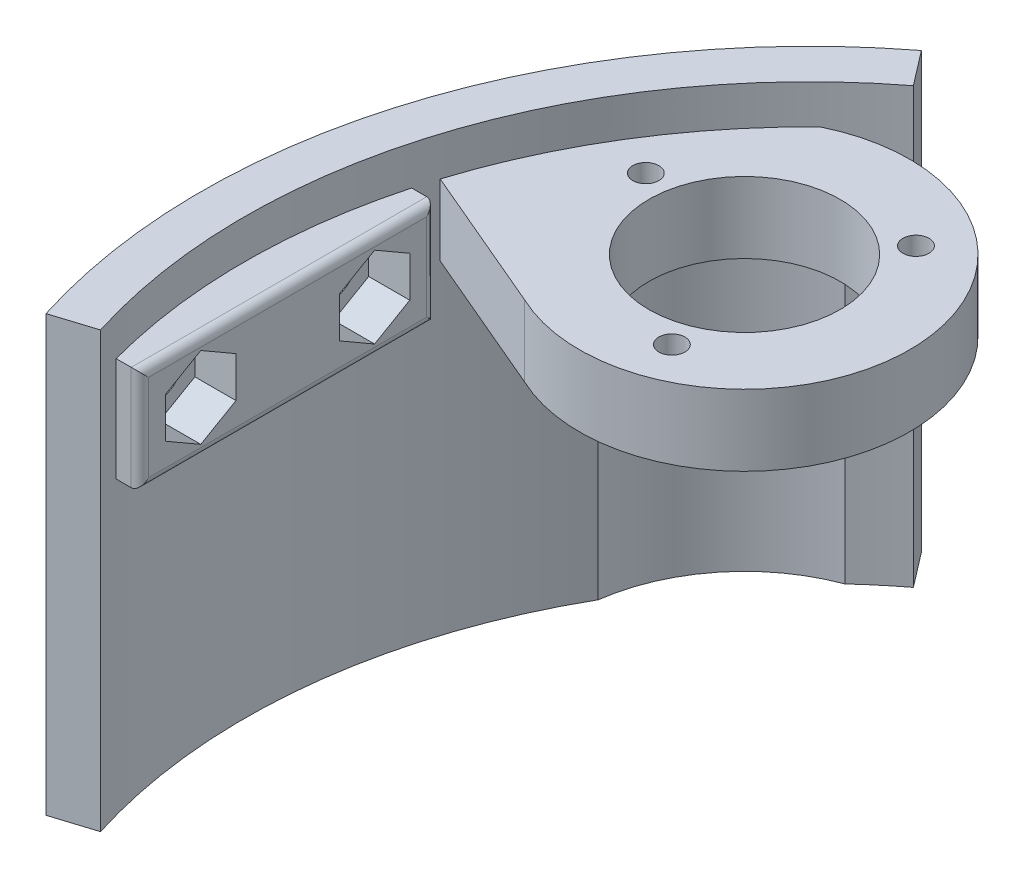
SolidWorks part; units mm, degrees
ref_plane "Front Plane" through (0, 0, 0) normal (0, 0, 1) x (1, 0, 0)
ref_plane "Top Plane" through (0, 0, 0) normal (0, 1, 0) x (1, 0, 0)
ref_plane "Right Plane" through (0, 0, 0) normal (1, 0, 0) x (0, 0, -1)
sketch "Sketch1" plane through (0, 0, 0) normal (0, 1, 0) x (1, 0, 0)
  line L2 (-66.7602, 21.0494) -> (0, 0)
  line L3 (0, 0) -> (-66.7602, -21.0494)
  line L4 (0, 0) -> (-66.7602, 21.0494)
  line L5 (-42.6133, 55.5347) -> (0, 0)
  line L6 (0, 0) -> (-61.9916, 19.5459) construction
  line L7 (0, 0) -> (-39.5695, 51.568) construction
  arc A0 (-66.7602, 21.0494) -> (-66.7602, -21.0494) centre (0, 0) ccw
  arc A1 (-61.9916, 19.5459) -> (-61.9916, -19.5459) centre (0, 0) ccw
  arc A2 (-39.5695, 51.568) -> (-61.9916, 19.5459) centre (0, 0) ccw
  arc A3 (-42.6133, 55.5347) -> (-66.7602, 21.0494) centre (0, 0) ccw
  point P8 (-65, 0)
  dimension "D1" = 140
  dimension "D2" = 5
  dimension "D3" = 35
  dimension "D5" = 35
  dimension "D4" = 2
extrude "Boss-Extrude1" add sketch "Sketch1" along normal blind 50 contours A1 L2 A0 L3 | L5 A3 L2 A2 region at (-54.462, 0, -38.1347) region at (-66.4858, 0, 0)
sketch "Sketch2" plane through (0, 0, 0) normal (0, 1, 0) x (1, 0, 0)
  line L0 (-66.7602, -21.0494) -> (-38.1487, -12.0282)
  line L1 (-38.1487, -12.0282) -> (0, -15.5)
  line L2 (0, -15.5) -> (0, 15.5)
  line L3 (0, 15.5) -> (-39.2471, 7.7244)
  line L4 (-67.8367, 13.3512) -> (-39.2471, 7.7244)
  circle A0 centre (0, 0) radius 40
  circle A1 centre (0, 0) radius 69.138
  arc A2 (-2.798, -15.2454) -> (-5.9097, 14.3292) centre (0, 0) ccw
  dimension "D1" = 80
  dimension "D2" = 31
extrude "Boss-Extrude2" add sketch "Sketch2" along normal blind 5 contours L4 A1 L0 A0 region at (-55.2007, 0, 3.0696)
sketch "Sketch3" plane through (0, 0, 0) normal (0, -1, 0) x (1, 0, 0)
  line L0 (-47.6858, 15.0353) -> (-38.1487, 12.0282)
  line L1 (-39.2471, -7.7244) -> (-49.0589, -9.6555)
  arc A0 (-38.1487, 12.0282) -> (-39.2471, -7.7244) centre (0, 0) ccw construction
  arc A1 (-38.1487, 12.0282) -> (-39.2471, -7.7244) centre (0, 0) ccw
  arc A2 (-47.6858, 15.0353) -> (-49.0589, -9.6555) centre (0, 0) ccw
  dimension "D1" = 10
extrude "Boss-Extrude3" add sketch "Sketch3" along normal blind 8.5
sketch "Sketch4" plane through (0, 0, 0) normal (0, 1, 0) x (1, 0, 0)
  line L0 (-66.7602, -21.0494) -> (-38.1487, -12.0282) construction
  line L1 (-38.1487, -12.0282) -> (0, -15.5) construction
  line L2 (0, -15.5) -> (0, 15.5) construction
  line L3 (0, 15.5) -> (-39.2471, 7.7244) construction
  line L4 (-67.8367, 13.3512) -> (-39.2471, 7.7244) construction
  line L5 (-66.7602, -21.0494) -> (-38.1487, -12.0282)
  line L6 (-38.1487, -12.0282) -> (0, -15.5)
  line L7 (0, -15.5) -> (0, 15.5)
  line L8 (0, 15.5) -> (-39.2471, 7.7244)
  line L9 (-67.8367, 13.3512) -> (-39.2471, 7.7244)
  circle A0 centre (0, 0) radius 15.5
  circle A1 centre (0, 0) radius 69.138
  circle A2 centre (0, 0) radius 69.138
  circle A3 centre (0, 0) radius 40
  circle A4 centre (0, 0) radius 40
  dimension "D1" = 0
  dimension "D2" = 0
extrude "Boss-Extrude4" add sketch "Sketch4" along normal blind 5 from surface contours L8 A4 L6 L7 | A0 region at (-25.3301, 0, 1.4883) starting at face at (-44.2329, -8.5, 2.4597)
sketch "Sketch5" plane through (0, -3.5, 0) normal (0, 1, 0) x (1, 0, 0)
  circle A0 centre (0, 0) radius 15.5
extrude "Boss-Extrude5" add sketch "Sketch5" along normal blind 7.17
sketch "Sketch7" plane through (0, 50, 0) normal (0, 1, 0) x (1, 0, 0)
  line L0 (-36.961, 29.5317) -> (-36.961, 0) construction
  line L1 (-36.961, 0) -> (0, 0) construction
  line L2 (0, 0) -> (-36.961, 29.5317) construction
  line L3 (-61.9916, 19.5459) -> (-45.0708, 12.3494)
  line L4 (-39.5695, 51.568) -> (-37.2381, 48.5297)
  line L6 (-42.6133, 55.5347) -> (-39.5695, 51.568) construction
  circle A0 centre (-36.961, 29.5317) radius 19
  arc A3 (-39.5695, 51.568) -> (-61.9916, -19.5459) centre (0, 0) ccw construction
  arc A4 (-39.5695, 51.568) -> (-61.9916, -19.5459) centre (0, 0) ccw
  arc M5 (-61.9916, -19.5459) -> (-39.5695, 51.568) centre (0, 0) cw
  dimension "D1" = 38
  dimension "D2" = 47.31
extrude "Boss-Extrude6" add sketch "Sketch7" against normal blind 8.18 from offset 4.5 contours A0 L4 L3 M5 | A0 region at (-56.4968, 50, -21.8557) region at (-36.7795, 50, -29.3867) offset against normal yes
sketch "Sketch8" plane through (0, 50, 0) normal (0, 1, 0) x (1, 0, 0)
  circle A0 centre (-36.961, 29.5317) radius 11
  circle A1 centre (-27.9647, 40.2587) radius 1.5
  circle A2 centre (-32.1693, 16.3773) radius 1.5
  circle A3 centre (-50.7489, 31.9592) radius 1.5
  point P12 (-36.961, 29.5317)
  dimension "D1" = 22
  dimension "D2" = 3
  dimension "D3" = 14
  dimension "D4" = 3
extrude "Cut-Extrude2" cut sketch "Sketch8" against normal up to next
sketch "Sketch10" plane through (0, 0, 0) normal (1, 0, 0) x (0, 0, -1)
  circle A0 centre (-10, 39.5) radius 2.55
  circle A1 centre (10, 39.5) radius 2.55
  dimension "D1" = 5.1
  dimension "D2" = 20
  dimension "D3" = 10
  dimension "D4" = 44.33
extrude "Cut-Extrude5" cut sketch "Sketch10" along normal up to next from offset 90 offset against normal yes
sketch "Sketch11" plane through (0, 0, 0) normal (1, 0, 0) x (0, 0, -1)
  line L1 (-10, 34.8235) -> (-5.95, 37.1617)
  line L2 (-5.95, 37.1617) -> (-5.95, 41.8383)
  line L3 (-5.95, 41.8383) -> (-10, 44.1765)
  line L4 (-10, 44.1765) -> (-14.05, 41.8383)
  line L5 (-14.05, 41.8383) -> (-14.05, 37.1617)
  line L6 (-14.05, 37.1617) -> (-10, 34.8235)
  line L7 (10, 34.8235) -> (14.05, 37.1617)
  line L8 (14.05, 37.1617) -> (14.05, 41.8383)
  line L9 (14.05, 41.8383) -> (10, 44.1765)
  line L10 (10, 44.1765) -> (5.95, 41.8383)
  line L11 (5.95, 41.8383) -> (5.95, 37.1617)
  line L12 (5.95, 37.1617) -> (10, 34.8235)
  line L13 (-17, 45.5) -> (17, 45.5)
  line L14 (-17, 45.5) -> (-17, 33.5)
  line L15 (-17, 33.5) -> (17, 33.5)
  line L16 (17, 45.5) -> (17, 33.5)
  circle A0 centre (-10, 39.5) radius 4.05 construction
  circle A1 centre (10, 39.5) radius 4.05 construction
  point P22 (0, 45.5)
  dimension "D1" = 8.1
  dimension "D2" = 8.1
  dimension "D3" = 12
  dimension "D4" = 34
  dimension "D5" = 10
  dimension "D6" = 6
extrude "Boss-Extrude7" add sketch "Sketch11" along normal blind 4 and the other way up to next from offset 64 offset against normal yes
sketch "Sketch12" plane through (-60, 0, 0) normal (1, 0, 0) x (0, 0, -1)
  line L6 (-10, 44.1765) -> (-14.05, 41.8383)
  line L7 (-14.05, 41.8383) -> (-14.05, 37.1617)
  line L8 (-14.05, 37.1617) -> (-10, 34.8235)
  line L9 (-10, 34.8235) -> (-5.95, 37.1617)
  line L10 (-5.95, 37.1617) -> (-5.95, 41.8383)
  line L11 (-5.95, 41.8383) -> (-10, 44.1765)
  line L12 (-10, 44.1765) -> (-14.05, 41.8383)
  line L13 (-14.05, 41.8383) -> (-14.05, 37.1617)
  line L14 (-14.05, 37.1617) -> (-10, 34.8235)
  line L15 (-10, 34.8235) -> (-5.95, 37.1617)
  line L16 (-5.95, 37.1617) -> (-5.95, 41.8383)
  line L17 (-5.95, 41.8383) -> (-10, 44.1765)
  line L18 (10, 44.1765) -> (5.95, 41.8383)
  line L19 (5.95, 41.8383) -> (5.95, 37.1617)
  line L20 (5.95, 37.1617) -> (10, 34.8235)
  line L21 (10, 34.8235) -> (14.05, 37.1617)
  line L22 (14.05, 37.1617) -> (14.05, 41.8383)
  line L23 (14.05, 41.8383) -> (10, 44.1765)
  line L24 (10, 44.1765) -> (5.95, 41.8383)
  line L25 (5.95, 41.8383) -> (5.95, 37.1617)
  line L26 (5.95, 37.1617) -> (10, 34.8235)
  line L27 (10, 34.8235) -> (14.05, 37.1617)
  line L28 (14.05, 37.1617) -> (14.05, 41.8383)
  line L29 (14.05, 41.8383) -> (10, 44.1765)
  dimension "D1" = 0
  dimension "D2" = 0
extrude "Cut-Extrude6" cut sketch "Sketch12" against normal up to vertex (4.7271 mm away) up to point (-64.7271, 37.1617, 5.95)
fillet "Fillet2" radius 2 1 edges at (-15.4149, -3.5, 1.6219)
fillet "Fillet5" radius 1 4 edges at (-60, 39.5, -17) (-60, 39.5, 17) (-60, 33.5, 0) (-60, 45.5, 0)
sketch "Sketch13" plane through (0, 3.67, 0) normal (0, 1, 0) x (1, 0, 0)
  circle A0 centre (0, 0) radius 4.5
  dimension "D1" = 9
extrude "Cut-Extrude7" cut sketch "Sketch13" against normal through all
sketch "Sketch14" plane through (0, -8.5, 0) normal (0, -1, 0) x (1, 0, 0)
  circle A0 centre (0, 0) radius 11
  dimension "D1" = 22
extrude "Cut-Extrude8" cut sketch "Sketch14" against normal blind 7
chamfer "Chamfer1" distance 0.5 angle 45 1 edges at (0, -8.5, -11)
chamfer "Chamfer2" distance 1 angle 45 1 edges at (0, -1.5, -4.5)
chamfer "Chamfer3" distance 5 angle 45 1 edges at (-39.9383, -3.5, 2.2209)
fillet "Fillet6" radius 2 3 edges at (-34.9449, -3.5, 1.9624) (-39.9383, 1.5, 2.2209) (-39.9383, 5, 2.2209)
sketch "Sketch16" plane through (0, 0, 0) normal (0, -1, 0) x (-1, 0, 0)
  circle A0 centre (36.961, 29.5317) radius 19.6883
  arc A4 (45.3218, 46.5933) -> (45.0708, 12.3494) centre (36.961, 29.5317) ccw construction
extrude "Cut-Extrude9" cut sketch "Sketch16" against normal up to surface (37.32 mm away) up to face at (-50.7489, 37.32, -30.4592)
sketch "Sketch17" plane through (0, 5, 0) normal (0, 1, 0) x (1, 0, 0)
  line L2 (-61.9916, -19.5459) -> (-40.0561, -12.6296)
  line L3 (-41.2094, 8.1106) -> (-63.7765, 12.5521)
  line L4 (-61.9916, -19.5459) -> (-40.0561, -12.6296)
  line L5 (-41.2094, 8.1106) -> (-63.7765, 12.5521)
  line L8 (-39.2471, 7.7244) -> (-49.0589, 9.6555)
  line L9 (-5.9097, 14.3292) -> (-39.2471, 7.7244)
  line L10 (-38.1487, -12.0282) -> (-2.798, -15.2454)
  line L11 (-47.6858, -15.0353) -> (-38.1487, -12.0282)
  line L12 (-39.2471, 7.7244) -> (-49.0589, 9.6555)
  line L13 (-5.9097, 14.3292) -> (-39.2471, 7.7244)
  line L14 (-38.1487, -12.0282) -> (-2.798, -15.2454)
  line L15 (-47.6858, -15.0353) -> (-38.1487, -12.0282)
  arc A2 (-41.2094, 8.1106) -> (-40.0561, -12.6296) centre (0, 0) ccw
  arc A3 (-63.7765, 12.5521) -> (-61.9916, -19.5459) centre (0, 0) ccw
  arc A5 (-63.7765, 12.5521) -> (-61.9916, -19.5459) centre (0, 0) ccw
  arc A6 (-2.798, -15.2454) -> (-5.9097, 14.3292) centre (0, 0) ccw
  arc A7 (-49.0589, 9.6555) -> (-47.6858, -15.0353) centre (0, 0) ccw
  arc A8 (-2.798, -15.2454) -> (-5.9097, 14.3292) centre (0, 0) ccw
  arc A9 (-49.0589, 9.6555) -> (-47.6858, -15.0353) centre (0, 0) ccw
  line M11 (-61.9916, -19.5459) -> (-40.0561, -12.6296)
  arc M12 (-40.0561, -12.6296) -> (-41.2094, 8.1106) centre (0, 0) cw
  line M13 (-41.2094, 8.1106) -> (-63.7765, 12.5521)
  arc M14 (-63.7765, 12.5521) -> (-61.9916, -19.5459) centre (0, 0) ccw
  dimension "D1" = 0
  dimension "D2" = 0
extrude "Cut-Extrude10" cut sketch "Sketch17" against normal through all contours L14 A8 L13 L12 L15 M12 | A9 L4 M13 M12 | A9 L5 M14 M11 region at (-57.1379, 5, 3.1773) region at (-45.5671, 5, 2.5339) region at (-12.2984, 5, 0.7189)
